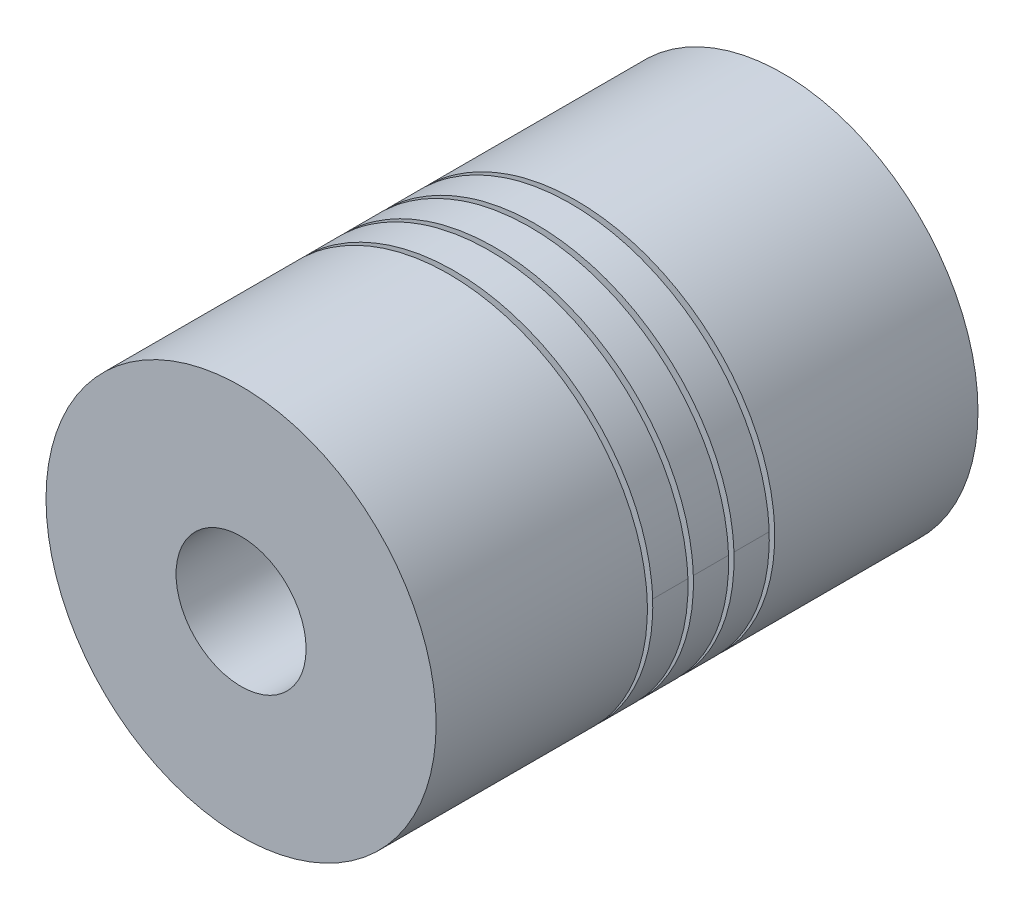
SolidWorks part; units mm, degrees
ref_plane "Front" through (0, 0, 0) normal (0, 0, 1) x (1, 0, 0)
ref_plane "Top" through (0, 0, 0) normal (0, 1, 0) x (1, 0, 0)
ref_plane "Right" through (0, 0, 0) normal (1, 0, 0) x (0, 0, -1)
sketch "Sketch1" plane through (0, 0, 0) normal (0, 0, 1) x (1, 0, 0)
  circle A0 centre (0, 0) radius 9
  dimension "D1" = 18
extrude "Boss-Extrude1" add sketch "Sketch1" along normal blind 25
sketch "Sketch2" plane through (0, 0, 25) normal (0, 0, 1) x (1, 0, 0)
  circle A0 centre (0, 0) radius 3
  dimension "D1" = 6
extrude "Cut-Extrude1" cut sketch "Sketch2" against normal blind 25
sketch "Sketch3" plane through (0, 0, 0) normal (0, 0, -1) x (-1, 0, 0)
  circle A0 centre (0, 0) radius 4
  dimension "D1" = 8
extrude "Cut-Extrude2" cut sketch "Sketch3" against normal blind 12.5
ref_plane "Plane1" through (0, 0, 16.6667) normal (0, 0, 1) x (1, 0, 0)
sketch "Sketch4" plane through (0, 0, 0) normal (1, 0, 0) x (0, 0, -1)
  line L0 (-16.6667, 9.9) -> (-16.6667, -9.9) construction
  line L1 (-16.6667, -1.3433) -> (-16.4167, -1.3433)
  line L2 (-16.6667, -1.3433) -> (-16.6667, -9.561)
  line L3 (-16.6667, -9.561) -> (-16.4167, -9.561)
  line L4 (-16.4167, -1.3433) -> (-16.4167, -9.561)
  point P6 (0, 0)
  point P7 (-15.6667, -10.8036)
  point P8 (-16.6667, -9.561)
  point P9 (-16.6667, -1.3433)
  dimension "D1" = 0.25
sketch "Sketch7" plane through (0, 0, 16.6667) normal (0, 0, 1) x (1, 0, 0)
  circle A0 centre (0, 0) radius 9
  circle A1 centre (0, 0) radius 9 construction
curve "Helix/Spiral1" pitch 1.875 height 7.5 turns 4
sweep "Cut-Sweep1" cut profiles "Sketch4" path "Helix/Spiral1" align with end faces yes
